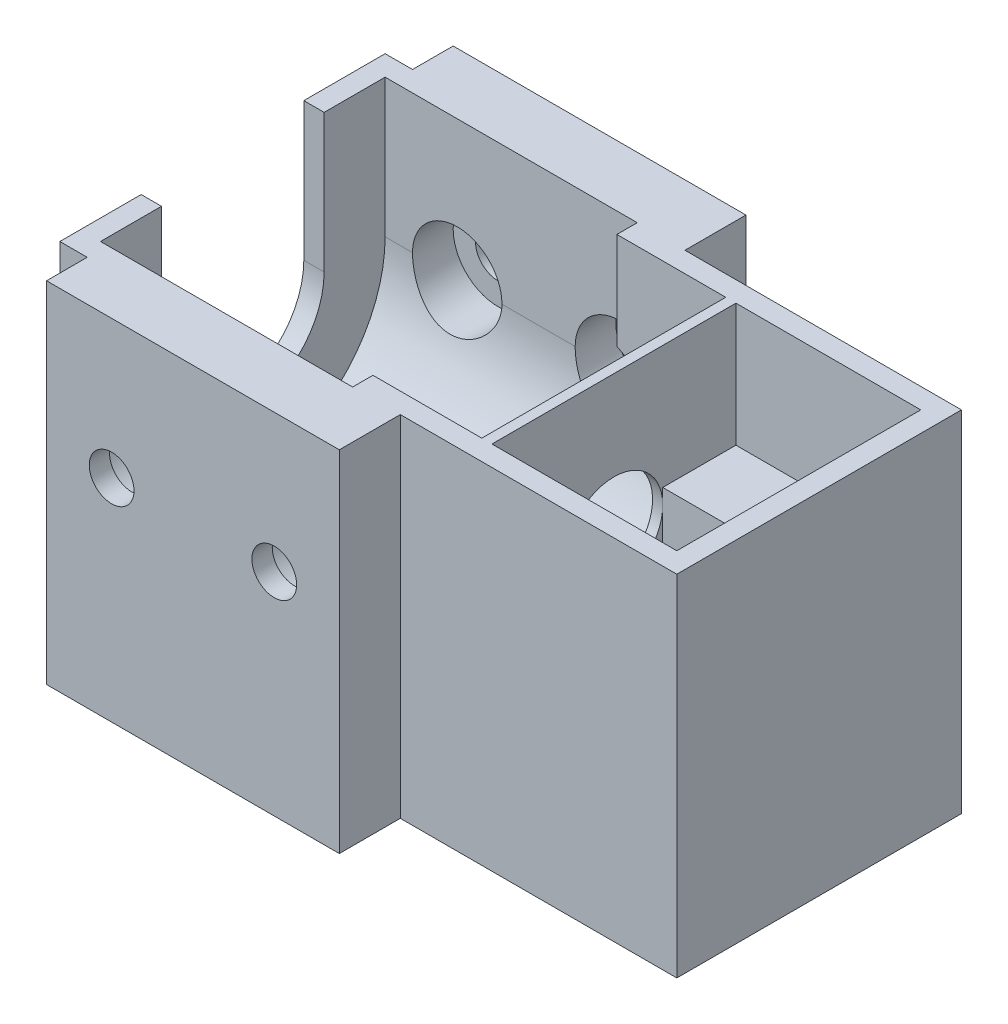
SolidWorks part; units mm, degrees
ref_plane "Front Plane" through (0, 0, 0) normal (0, 0, 1) x (1, 0, 0)
ref_plane "Top Plane" through (0, 0, 0) normal (0, 1, 0) x (1, 0, 0)
ref_plane "Right Plane" through (0, 0, 0) normal (1, 0, 0) x (0, 0, -1)
sketch "Sketch1" plane through (0, 0, 0) normal (0, 0, 1) x (1, 0, 0)
  line L1 (-76.2, -50.8) -> (40.64, -50.8)
  line L2 (-76.2, -50.8) -> (-76.2, 0)
  line L3 (-76.2, 0) -> (40.64, 0)
  line L4 (40.64, -50.8) -> (40.64, 0)
  line L5 (-76.2, -50.8) -> (40.64, 0) construction
  line L6 (-76.2, 0) -> (40.64, -50.8) construction
  point P0 (0, 0)
  dimension "D1" = 116.84
  dimension "D2" = 50.8
  dimension "D3" = 76.2
extrude "Boss-Extrude1" add sketch "Sketch1" along normal mid plane 63.5
sketch "Sketch2" plane through (0, 0, 0) normal (0, 0, 1) x (1, 0, 0)
  line L0 (-152.4829, -25.4) -> (9.3782, -25.4) construction
  line L1 (-49.3609, -3.175) -> (-49.3609, -12.7)
  line L2 (40.64, 0) -> (-76.2, 0) construction
  line L3 (40.64, 0) -> (-76.2, 0) construction
  line L4 (-9.9909, -3.175) -> (-9.9909, -6.35)
  line L5 (-9.9909, -25.4) -> (-9.9909, -3.175) construction
  line L6 (-128.4172, -25.4) -> (-157.8092, -25.4)
  line L7 (9.3782, -25.4) -> (40.64, -25.4)
  line L8 (-607.3619, -25.4) -> (9.3782, -25.4) construction
  line L9 (-49.3609, -3.175) -> (-9.9909, -3.175)
  line L10 (9.3782, -25.4) -> (-128.4172, -25.4)
  line L11 (-9.9909, -6.35) -> (7.0091, -6.35)
  line L12 (7.0091, -6.35) -> (7.0091, -17.78)
  line L13 (7.0091, -17.78) -> (25.0091, -17.78)
  line L14 (-49.3609, -12.7) -> (-220.2024, -12.7)
  line L15 (-220.2024, -12.7) -> (-220.2024, -25.4)
  line L16 (-220.2024, -25.4) -> (-157.8092, -25.4)
  line L17 (25.0091, -17.78) -> (25.0091, -25.4) construction
  line L18 (25.0091, -17.78) -> (40.64, -17.78)
  line L19 (40.64, -50.8) -> (40.64, 0) construction
  line L20 (40.64, -17.78) -> (40.64, -25.4)
  line L21 (-76.2, 0) -> (-76.2, -50.8) construction
  point P23 (-9.9909, -25.4)
  dimension "D1" = 22.225
  dimension "D2" = 39.37
  dimension "D3" = 25.4
  dimension "D4" = 35
  dimension "D5" = 7.62
  dimension "D6" = 3.175
  dimension "D7" = 26.8391
  dimension "D8" = 18
  dimension "D9" = 12.7
revolve "Cut-Revolve1" cut sketch "Sketch2" angle 360 about L0
sketch "Sketch38" plane through (40.64, 0, 0) normal (1, 0, 0) x (0, 0, -1)
  line L1 (-10, -35.4) -> (10, -35.4)
  line L2 (-10, -35.4) -> (-10, -15.4)
  line L3 (-10, -15.4) -> (10, -15.4)
  line L4 (10, -35.4) -> (10, -15.4)
  line L5 (-10, -35.4) -> (10, -15.4) construction
  line L6 (-10, -15.4) -> (10, -35.4) construction
  point P0 (0, -25.4)
  point P1 (0, -25.4)
  dimension "D1" = 20
  dimension "D2" = 20
extrude "Cut-Extrude33" cut sketch "Sketch38" against normal offset from surface (32.0434 mm away) 1.5875 up to face at (7.0091, -44.45, 0)
sketch "Sketch37" plane through (40.64, 0, 0) normal (1, 0, 0) x (0, 0, -1)
  line L0 (31.75, -50.8) -> (31.75, 0) construction
  line L1 (-31.75, 0) -> (31.75, 0)
  line L2 (-31.75, 0) -> (-31.75, -25.4)
  line L3 (-31.75, -25.4) -> (31.75, -25.4)
  line L4 (31.75, 0) -> (31.75, -25.4)
  line L5 (10, -35.4) -> (10, -15.4) construction
  point P7 (0, -25.4)
  point P11 (0, 0)
  point P14 (10, -25.4)
extrude "Cut-Extrude32" cut sketch "Sketch37" against normal through all
sketch "Sketch39" plane through (0, -25.4, 0) normal (0, 1, 0) x (1, 0, 0)
  line L10 (-76.2, 12.7) -> (-49.3609, 12.7)
  line L11 (-49.3609, 12.7) -> (-49.3609, 22.225)
  line L12 (-49.3609, 22.225) -> (-9.9909, 22.225)
  line L13 (-9.9909, 22.225) -> (-9.9909, 19.05)
  line L14 (-9.9909, 19.05) -> (7.0091, 19.05)
  line L15 (7.0091, 19.05) -> (7.0091, 7.62)
  line L16 (7.0091, 19.05) -> (7.0091, 7.62)
  line L17 (40.64, 10) -> (40.64, 31.75)
  line L18 (40.64, 31.75) -> (-76.2, 31.75)
  line L19 (-76.2, 31.75) -> (-76.2, 12.7)
  line L20 (-76.2, 12.7) -> (-49.3609, 12.7)
  line L21 (-49.3609, 12.7) -> (-49.3609, 22.225)
  line L22 (-49.3609, 22.225) -> (-9.9909, 22.225)
  line L23 (-9.9909, 22.225) -> (-9.9909, 19.05)
  line L24 (-9.9909, 19.05) -> (7.0091, 19.05)
  line L25 (8.5966, 10) -> (40.64, 10)
  line L26 (8.5966, 10) -> (40.64, 10)
  line L27 (40.64, 10) -> (40.64, 31.75)
  line L28 (40.64, 31.75) -> (-76.2, 31.75)
  line L29 (-76.2, 31.75) -> (-76.2, 12.7)
  line L30 (-49.3609, -12.7) -> (-76.2, -12.7)
  line L31 (-76.2, -12.7) -> (-76.2, -31.75)
  line L32 (-76.2, -31.75) -> (40.64, -31.75)
  line L33 (40.64, -31.75) -> (40.64, -10)
  line L34 (40.64, -10) -> (8.5966, -10)
  line L35 (40.64, -10) -> (8.5966, -10)
  line L36 (7.0091, -19.05) -> (-9.9909, -19.05)
  line L37 (-9.9909, -19.05) -> (-9.9909, -22.225)
  line L38 (-9.9909, -22.225) -> (-49.3609, -22.225)
  line L39 (-49.3609, -22.225) -> (-49.3609, -12.7)
  line L40 (-49.3609, -12.7) -> (-76.2, -12.7)
  line L41 (-76.2, -12.7) -> (-76.2, -31.75)
  line L42 (-76.2, -31.75) -> (40.64, -31.75)
  line L43 (40.64, -31.75) -> (40.64, -10)
  line L44 (7.0091, -7.62) -> (7.0091, -19.05)
  line L45 (7.0091, -7.62) -> (7.0091, -19.05)
  line L46 (7.0091, -19.05) -> (-9.9909, -19.05)
  line L47 (-9.9909, -19.05) -> (-9.9909, -22.225)
  line L48 (-9.9909, -22.225) -> (-49.3609, -22.225)
  line L49 (-49.3609, -22.225) -> (-49.3609, -12.7)
  line L52 (7.0091, 7.62) -> (8.5966, 7.62)
  line L53 (7.0091, 7.62) -> (8.5966, 7.62)
  line L54 (8.5966, 7.62) -> (8.5966, 10)
  line L55 (8.5966, 7.62) -> (8.5966, 10)
  line L56 (8.5966, -10) -> (8.5966, -7.62)
  line L57 (8.5966, -10) -> (8.5966, -7.62)
  line L58 (8.5966, -7.62) -> (7.0091, -7.62)
  line L59 (8.5966, -7.62) -> (7.0091, -7.62)
  dimension "D1" = 0
  dimension "D2" = 0
extrude "Boss-Extrude5" add sketch "Sketch39" along normal blind 25.4
sketch "Sketch40" plane through (0, 0, 0) normal (0, 1, 0) x (1, 0, 0)
  line L0 (8.5966, 10) -> (40.64, 10) construction
  line L1 (25.0091, 10) -> (40.64, 10)
  line L2 (25.0091, 10) -> (25.0091, -10)
  line L3 (25.0091, -10) -> (40.64, -10)
  line L4 (40.64, 10) -> (40.64, -10)
  line L6 (-9.9909, 22.225) -> (-9.9909, 19.05) construction
  dimension "D1" = 35
extrude "Boss-Extrude6" add sketch "Sketch40" against normal up to next
sketch "Sketch41" plane through (0, 0, 0) normal (0, 1, 0) x (1, 0, 0)
  line L2 (-76.2, 12.7) -> (-76.2, -12.7) construction
  circle A0 centre (-57.15, 0) radius 3.1134
  circle A1 centre (-31.75, 0) radius 3.1134
  circle A2 centre (-6.35, 0) radius 3.1134
  dimension "D1" = 19.05
extrude "Cut-Extrude34" cut sketch "Sketch41" against normal through all
ref_plane "Plane_Mid" through (0, -25.4, 0) normal (0, 1, 0) x (1, 0, 0)
ref_axis "Axis1" through (8.5966, -25.4, 0) along (-1, 0, 0)
sketch "Sketch42" plane through (0, 0, 0) normal (0, 0, 1) x (1, 0, 0)
  line L0 (1.7462, -25.4) -> (-1.7462, -25.4) construction
  line L1 (-76.2, 0) -> (-76.2, -25.4) construction
  circle A0 centre (-38.1, -25.4) radius 3.4925
  circle A1 centre (-12.7, -25.4) radius 3.4925
  dimension "D1" = 6.985
  dimension "D2" = 38.1
extrude "Cut-Extrude35" cut sketch "Sketch42" against normal through all both and the other way through all
sketch "Sketch43" plane through (0, 0, 0) normal (0, 0, 1) x (1, 0, 0)
  circle A0 centre (-38.1, -25.4) radius 6.985
  circle A1 centre (-12.7, -25.4) radius 6.985
  dimension "D1" = 13.97
extrude "Cut-Extrude36" cut sketch "Sketch43" against normal offset from surface (28.575 mm away) 3.175 up to face at (-9.2075, -25.4, -31.75)
extrude "Cut-Extrude37" cut sketch "Sketch43<2>" along normal offset from surface (28.575 mm away) 3.175 up to face at (-9.2075, -25.4, 31.75)
sketch "Sketch43<2>" plane through (0, 0, 0) normal (0, 0, 1) x (1, 0, 0) same geometry as "Sketch43"
sketch "Sketch44" plane through (0, 0, 0) normal (0, 1, 0) x (1, 0, 0)
  line L0 (7.0091, -19.05) -> (-9.9909, -19.05) construction
  line L1 (8.5966, 19.05) -> (24.5091, 19.05)
  line L2 (8.5966, 19.05) -> (8.5966, -19.05)
  line L3 (8.5966, -19.05) -> (24.5091, -19.05)
  line L4 (24.5091, 19.05) -> (24.5091, -19.05)
  line L5 (-9.9909, 19.05) -> (7.0091, 19.05) construction
  line L6 (8.5966, 7.62) -> (8.5966, 10) construction
  line L7 (25.0091, 10) -> (25.0091, -10) construction
  dimension "D1" = 0.5
extrude "Cut-Extrude38" cut sketch "Sketch44" against normal up to surface (35.4 mm away) up to face at (16.8028, -35.4, 0)
sketch "Sketch45" plane through (0, 0, 0) normal (0, 0, 1) x (1, 0, 0)
  line L0 (40.64, 0) -> (-76.2, 0) construction
  line L2 (37.465, 0) -> (24.5091, 0)
  line L4 (37.465, 0) -> (37.465, -15.4)
  line L5 (37.465, -15.4) -> (24.5091, -15.4)
  line L8 (24.5091, 0) -> (24.5091, -15.4)
  line L9 (40.64, -50.8) -> (40.64, 0) construction
  line L10 (24.5091, -35.4) -> (24.5091, 0) construction
  line L11 (-5.715, -25.4) -> (7.0091, -25.4) construction
  dimension "D1" = 3.175
  dimension "D2" = 10
extrude "Cut-Extrude39" cut sketch "Sketch45" against normal up to surface and the other way up to surface up to face at (16.5528, -17.7, -19.05) other way up to face at (16.5529, -17.7, 19.05)
sketch "Sketch46" plane through (0, 0, 0) normal (0, 1, 0) x (1, 0, 0)
  line L0 (-9.9909, 19.05) -> (7.0091, 19.05) construction
  line L1 (40.64, 31.75) -> (-2.54, 31.75)
  line L2 (40.64, 31.75) -> (40.64, 22.225)
  line L3 (40.64, 22.225) -> (-2.54, 22.225)
  line L4 (-2.54, 31.75) -> (-2.54, 22.225)
  line L5 (-76.2, 0) -> (40.64, 0) construction
  line L6 (-76.2, 12.7) -> (-76.2, -12.7) construction
  line L7 (40.64, -31.75) -> (40.64, 31.75) construction
  line L8 (40.64, -31.75) -> (40.64, -22.225)
  line L9 (40.64, -22.225) -> (-2.54, -22.225)
  line L10 (40.64, -31.75) -> (-2.54, -31.75)
  line L11 (-2.54, -31.75) -> (-2.54, -22.225)
  line L12 (-49.3609, 22.225) -> (-9.9909, 22.225) construction
  line L13 (-76.2, 31.75) -> (-48.26, 31.75)
  line L14 (-76.2, 31.75) -> (-76.2, 25.4)
  line L15 (-76.2, 25.4) -> (-48.26, 25.4)
  line L16 (-48.26, 31.75) -> (-48.26, 25.4)
  line L17 (-48.26, -31.75) -> (-48.26, -25.4)
  line L18 (-76.2, -25.4) -> (-48.26, -25.4)
  line L19 (-76.2, -31.75) -> (-76.2, -25.4)
  line L20 (-76.2, -31.75) -> (-48.26, -31.75)
  dimension "D1" = 3.175
  dimension "D2" = 3.175
  dimension "D3" = 3.175
  dimension "D4" = 3.175
extrude "Cut-Extrude40" cut sketch "Sketch46" against normal through all
sketch "Sketch49" plane through (0, 0, 0) normal (0, 1, 0) x (1, 0, 0)
  line L0 (-48.26, -25.4) -> (-76.2, -25.4) construction
  line L1 (-76.2, 25.4) -> (-52.5359, 25.4)
  line L2 (-76.2, 25.4) -> (-76.2, -25.4)
  line L3 (-76.2, -25.4) -> (-52.5359, -25.4)
  line L4 (-52.5359, 25.4) -> (-52.5359, -25.4)
  line L5 (-49.3609, -22.225) -> (-49.3609, 22.225) construction
  dimension "D1" = 3.175
extrude "Cut-Extrude42" cut sketch "Sketch49" against normal through all
sketch "Sketch50" plane through (0, 0, 0) normal (0, 1, 0) x (1, 0, 0)
  line L0 (-2.54, 22.225) -> (40.64, 22.225) construction
  line L1 (24.2551, 20.701) -> (24.5091, 20.701)
  line L2 (24.2551, 20.701) -> (24.2551, 22.225)
  line L3 (24.2551, 22.225) -> (24.5091, 22.225)
  line L4 (24.5091, 20.701) -> (24.5091, 22.225)
  line L5 (24.3821, 22.225) -> (24.3821, 20.701) construction
  line L6 (24.2551, 21.463) -> (24.5091, 21.463) construction
  line L8 (24.5091, 10) -> (24.5091, 19.05) construction
  line L9 (22.7311, 20.701) -> (22.9851, 20.701)
  line L10 (22.9851, 20.701) -> (22.9851, 22.225)
  line L11 (22.7311, 22.225) -> (22.9851, 22.225)
  line L12 (22.7311, 20.701) -> (22.7311, 22.225)
  line L13 (21.2071, 20.701) -> (21.4611, 20.701)
  line L14 (21.4611, 20.701) -> (21.4611, 22.225)
  line L15 (21.2071, 22.225) -> (21.4611, 22.225)
  line L16 (21.2071, 20.701) -> (21.2071, 22.225)
  line L17 (19.6831, 20.701) -> (19.9371, 20.701)
  line L18 (19.9371, 20.701) -> (19.9371, 22.225)
  line L19 (19.6831, 22.225) -> (19.9371, 22.225)
  line L20 (19.6831, 20.701) -> (19.6831, 22.225)
  line L21 (18.1591, 20.701) -> (18.4131, 20.701)
  line L22 (18.4131, 20.701) -> (18.4131, 22.225)
  line L23 (18.1591, 22.225) -> (18.4131, 22.225)
  line L24 (18.1591, 20.701) -> (18.1591, 22.225)
  line L25 (16.6351, 20.701) -> (16.8891, 20.701)
  line L26 (16.8891, 20.701) -> (16.8891, 22.225)
  line L27 (16.6351, 22.225) -> (16.8891, 22.225)
  line L28 (16.6351, 20.701) -> (16.6351, 22.225)
  line L29 (15.1111, 20.701) -> (15.3651, 20.701)
  line L30 (15.3651, 20.701) -> (15.3651, 22.225)
  line L31 (15.1111, 22.225) -> (15.3651, 22.225)
  line L32 (15.1111, 20.701) -> (15.1111, 22.225)
  line L33 (13.5871, 20.701) -> (13.8411, 20.701)
  line L34 (13.8411, 20.701) -> (13.8411, 22.225)
  line L35 (13.5871, 22.225) -> (13.8411, 22.225)
  line L36 (13.5871, 20.701) -> (13.5871, 22.225)
  line L37 (12.0631, 20.701) -> (12.3171, 20.701)
  line L38 (12.3171, 20.701) -> (12.3171, 22.225)
  line L39 (12.0631, 22.225) -> (12.3171, 22.225)
  line L40 (12.0631, 20.701) -> (12.0631, 22.225)
  line L41 (10.5391, 20.701) -> (10.7931, 20.701)
  line L42 (10.7931, 20.701) -> (10.7931, 22.225)
  line L43 (10.5391, 22.225) -> (10.7931, 22.225)
  line L44 (10.5391, 20.701) -> (10.5391, 22.225)
  point P0 (24.3821, 21.463)
  dimension "D1" = 0.254
  dimension "D2" = 1.524
  dimension "D3" = 10
extrude "Cut-Extrude43" cut sketch "Sketch50" against normal blind 2.54
sketch "Sketch52" plane through (25.0091, 0, 0) normal (-1, 0, 0) x (0, 0, 1)
  circle A0 centre (0, -25.4) radius 0.3175
  dimension "D1" = 0.635
extrude "Cut-Extrude45" cut sketch "Sketch52" against normal blind 0.0508
sketch "Sketch53" plane through (25.0091, 0, 0) normal (-1, 0, 0) x (0, 0, 1)
  circle A0 centre (0, -25.4) radius 2
  dimension "D1" = 4
extrude "Cut-Extrude46" cut sketch "Sketch53" against normal blind 0.0254
sketch "Sketch54" plane through (0, -35.4, 0) normal (0, 1, 0) x (1, 0, 0)
  line L0 (24.5091, 10) -> (24.5091, -10)
  line L8 (25.0091, 10) -> (24.5091, 10)
  line L9 (24.5091, 10) -> (24.5091, 19.05)
  line L10 (24.5091, 19.05) -> (8.5966, 19.05)
  line L11 (8.5966, 19.05) -> (8.5966, -19.05)
  line L12 (8.5966, -19.05) -> (24.5091, -19.05)
  line L13 (24.5091, -19.05) -> (24.5091, -10)
  line L14 (24.5091, -10) -> (25.0091, -10)
  line L15 (25.0091, -10) -> (25.0091, 10)
  line L17 (24.5091, 10) -> (24.5091, 19.05)
  line L18 (24.5091, 19.05) -> (8.5966, 19.05)
  line L19 (8.5966, 19.05) -> (8.5966, -19.05)
  line L20 (8.5966, -19.05) -> (24.5091, -19.05)
  line L21 (24.5091, -19.05) -> (24.5091, -10)
  dimension "D1" = 0
extrude "Boss-Extrude7" add sketch "Sketch54" along normal blind 2.54
sketch "Sketch55" plane through (0, -32.86, 0) normal (0, 1, 0) x (1, 0, 0)
  line L0 (24.5091, -19.05) -> (24.5091, -10) construction
  line L1 (24.5091, 10) -> (8.5966, 10)
  line L2 (24.5091, 10) -> (24.5091, 19.05)
  line L3 (24.5091, 19.05) -> (8.5966, 19.05)
  line L4 (8.5966, 10) -> (8.5966, 19.05)
  line L5 (24.5091, 10) -> (8.5966, 19.05) construction
  line L6 (24.5091, 19.05) -> (8.5966, 10) construction
  line L7 (8.5966, -19.05) -> (24.5091, -19.05)
  line L8 (8.5966, -19.05) -> (8.5966, -10)
  line L9 (8.5966, -10) -> (24.5091, -10)
  line L10 (24.5091, -19.05) -> (24.5091, -10)
  line L11 (8.5966, -19.05) -> (24.5091, -10) construction
  line L12 (8.5966, -10) -> (24.5091, -19.05) construction
  point P4 (16.5528, 14.525)
  point P11 (16.5528, -14.525)
extrude "Boss-Extrude8" add sketch "Sketch55" along normal up to surface (17.46 mm away) up to face at (27.8731, -15.4, 0)
sketch "Sketch56" plane through (0, 0, 0) normal (0, 0, 1) x (1, 0, 0)
  line L0 (18.1591, -27.4) -> (18.1591, -32.86) construction
  line L1 (25.0345, -27.4) -> (18.1591, -27.4) construction
  line L2 (25.0345, -23.4) -> (25.0345, -27.4) construction
  line L3 (8.5966, -25.4) -> (7.0091, -25.4) construction
  line L4 (8.5966, -32.86) -> (8.5966, -25.4) construction
  line L5 (13.3779, -30.13) -> (8.5966, -30.13) construction
  line L6 (13.3779, -30.13) -> (18.1591, -30.13) construction
  line L7 (18.1591, -27.4) -> (24.5091, -27.4)
  line L8 (24.5091, -27.4) -> (24.5091, -32.86)
  line L9 (8.5966, -32.86) -> (24.5091, -32.86)
  spline S0 degree 3 poles (8.5966, -32.86) (9.5288, -32.86) (16.4945, -27.986) (16.8413, -27.4) (18.1591, -27.4) knots 0 0 0 0 0.327131 1 1 1 1
  point P6 (18.1591, -30.13)
  dimension "D1" = 2
  dimension "D2" = 6.35
extrude "Boss-Extrude9" add sketch "Sketch56" along normal up to next and the other way up to next
sketch "Sketch57" plane through (0, -15.4, 0) normal (0, 1, 0) x (1, 0, 0)
  line L8 (25.0091, -10) -> (8.5966, -10)
  line L9 (8.5966, -10) -> (8.5966, -19.05)
  line L10 (8.5966, -19.05) -> (37.465, -19.05)
  line L11 (37.465, -19.05) -> (37.465, 19.05)
  line L12 (37.465, 19.05) -> (8.5966, 19.05)
  line L13 (25.0091, -10) -> (8.5966, -10)
  line L14 (8.5966, 19.05) -> (8.5966, 10)
  line L15 (25.0091, 10) -> (25.0091, -10)
  line L16 (8.5966, 19.05) -> (8.5966, 10)
  line L17 (8.5966, -10) -> (8.5966, -19.05)
  line L18 (8.5966, -19.05) -> (37.465, -19.05)
  line L19 (37.465, -19.05) -> (37.465, 19.05)
  line L20 (37.465, 19.05) -> (8.5966, 19.05)
  line L21 (8.5966, 10) -> (25.0091, 10)
  line L22 (8.5966, 10) -> (25.0091, 10)
  line L23 (25.0091, 10) -> (25.0091, -10)
  dimension "D1" = 0
extrude "Cut-Extrude47" cut sketch "Sketch57" against normal blind 7.62
sketch "Sketch58" plane through (0, -50.8, 0) normal (0, -1, 0) x (1, 0, 0)
  line L12 (-48.26, 25.4) -> (-52.5359, 25.4)
  line L13 (-52.5359, 25.4) -> (-52.5359, -25.4)
  line L14 (-52.5359, -25.4) -> (-48.26, -25.4)
  line L15 (-48.26, -25.4) -> (-48.26, -31.75)
  line L16 (-48.26, -31.75) -> (-2.54, -31.75)
  line L17 (-2.54, -31.75) -> (-2.54, -22.225)
  line L18 (-2.54, -22.225) -> (40.64, -22.225)
  line L19 (40.64, -22.225) -> (40.64, 22.225)
  line L20 (40.64, 22.225) -> (-2.54, 22.225)
  line L21 (-2.54, 22.225) -> (-2.54, 31.75)
  line L22 (-2.54, 31.75) -> (-48.26, 31.75)
  line L23 (-48.26, 31.75) -> (-48.26, 25.4)
  line L24 (-48.26, 25.4) -> (-52.5359, 25.4)
  line L25 (-52.5359, 25.4) -> (-52.5359, -25.4)
  line L26 (-52.5359, -25.4) -> (-48.26, -25.4)
  line L27 (-48.26, -25.4) -> (-48.26, -31.75)
  line L28 (-48.26, -31.75) -> (-2.54, -31.75)
  line L29 (-2.54, -31.75) -> (-2.54, -22.225)
  line L30 (-2.54, -22.225) -> (40.64, -22.225)
  line L31 (40.64, -22.225) -> (40.64, 22.225)
  line L32 (40.64, 22.225) -> (-2.54, 22.225)
  line L33 (-2.54, 22.225) -> (-2.54, 31.75)
  line L34 (-2.54, 31.75) -> (-48.26, 31.75)
  line L35 (-48.26, 31.75) -> (-48.26, 25.4)
  circle A0 centre (-31.75, 0) radius 3.1134
  circle A1 centre (-6.35, 0) radius 3.1134
  circle A2 centre (-6.35, 0) radius 3.1134 construction
  circle A3 centre (-31.75, 0) radius 3.1134 construction
  dimension "D1" = 0
extrude "Boss-Extrude10" add sketch "Sketch58" along normal blind 7.62
sketch "Sketch59" plane through (0, -35.4, 0) normal (0, 1, 0) x (1, 0, 0)
  line L4 (24.5091, 10) -> (24.5091, -10)
  line L5 (24.5091, -10) -> (25.0091, -10)
  line L6 (25.0091, -10) -> (25.0091, 10)
  line L7 (25.0091, 10) -> (24.5091, 10)
  line L8 (24.5091, 10) -> (24.5091, -10)
  line L9 (24.5091, -10) -> (25.0091, -10)
  line L10 (25.0091, -10) -> (25.0091, 10)
  line L11 (25.0091, 10) -> (24.5091, 10)
  dimension "D1" = 0
extrude "Cut-Extrude48" cut sketch "Sketch59" against normal blind 7.62
sketch "Sketch51" plane through (0, -23.02, 0) normal (0, 1, 0) x (1, 0, 0)
  line L0 (26.2025, 0.254) -> (27.2127, 0.254)
  line L1 (25.6945, 2.54) -> (26.2025, 2.54)
  line L2 (25.6945, 2.54) -> (25.6945, 0.254)
  line L3 (25.6945, -2.54) -> (26.2025, -2.54)
  line L4 (26.2025, 2.54) -> (26.2025, 0.254)
  line L5 (30.7571, -0.254) -> (31.7673, -0.254)
  line L6 (26.2025, -0.254) -> (26.2025, -2.54)
  line L7 (27.7207, 2.54) -> (27.7207, 0.254)
  line L8 (27.2127, 2.54) -> (27.7207, 2.54)
  line L9 (27.2127, 2.54) -> (27.2127, 0.254)
  line L10 (27.2127, -2.54) -> (27.7207, -2.54)
  line L11 (29.2389, 2.54) -> (29.2389, 0.254)
  line L12 (28.7309, 2.54) -> (29.2389, 2.54)
  line L13 (28.7309, 2.54) -> (28.7309, 0.254)
  line L14 (28.7309, -2.54) -> (29.2389, -2.54)
  line L15 (30.7571, 2.54) -> (30.7571, 0.254)
  line L16 (30.2491, 2.54) -> (30.7571, 2.54)
  line L17 (30.2491, 2.54) -> (30.2491, 0.254)
  line L18 (30.2491, -2.54) -> (30.7571, -2.54)
  line L19 (32.2753, 2.54) -> (32.2753, 0.254)
  line L20 (31.7673, 2.54) -> (32.2753, 2.54)
  line L21 (31.7673, 2.54) -> (31.7673, 0.254)
  line L22 (31.7673, -2.54) -> (32.2753, -2.54)
  line L23 (33.7936, 2.54) -> (33.7936, 0.254)
  line L24 (33.2856, 2.54) -> (33.7936, 2.54)
  line L25 (33.2856, 2.54) -> (33.2856, 0.254)
  line L26 (33.2856, -2.54) -> (33.7936, -2.54)
  line L27 (35.3118, 2.54) -> (35.3118, 0.254)
  line L28 (34.8038, 2.54) -> (35.3118, 2.54)
  line L29 (34.8038, 2.54) -> (34.8038, 0.254)
  line L30 (34.8038, -2.54) -> (35.3118, -2.54)
  line L31 (36.83, 2.54) -> (36.83, 0.254)
  line L32 (36.322, 2.54) -> (36.83, 2.54)
  line L33 (36.322, 2.54) -> (36.322, 0.254)
  line L34 (36.322, -2.54) -> (36.83, -2.54)
  line L35 (35.258, 2.5876) -> (25.851, 2.5876) construction
  line L36 (23.32, 11.7754) -> (37.465, 11.7754) construction
  line L37 (26.2025, -0.254) -> (27.2127, -0.254)
  line L38 (25.0091, 10) -> (25.0091, -10) construction
  line L39 (37.465, -19.05) -> (37.465, 19.05) construction
  line L40 (25.0091, 0.254) -> (25.6945, 0.254)
  line L41 (25.0091, 0.254) -> (25.0091, -0.254)
  line L42 (25.0091, -0.254) -> (25.6945, -0.254)
  line L43 (37.465, 0.254) -> (37.465, -0.254)
  line L44 (32.2753, 0.254) -> (33.2856, 0.254)
  line L46 (25.6945, -0.254) -> (25.6945, -2.54)
  line L47 (27.2127, -0.254) -> (27.2127, -2.54)
  line L48 (27.7207, 0.254) -> (28.7309, 0.254)
  line L49 (27.7207, -0.254) -> (27.7207, -2.54)
  line L51 (27.7207, -0.254) -> (28.7309, -0.254)
  line L52 (28.7309, -0.254) -> (28.7309, -2.54)
  line L53 (29.2389, 0.254) -> (30.2491, 0.254)
  line L54 (29.2389, -0.254) -> (30.2491, -0.254)
  line L55 (29.2389, -0.254) -> (29.2389, -2.54)
  line L56 (30.2491, -0.254) -> (30.2491, -2.54)
  line L57 (30.7571, 0.254) -> (31.7673, 0.254)
  line L58 (32.2753, -0.254) -> (33.2856, -0.254)
  line L61 (30.7571, -0.254) -> (30.7571, -2.54)
  line L62 (31.7673, -0.254) -> (31.7673, -2.54)
  line L63 (32.2753, -0.254) -> (32.2753, -2.54)
  line L64 (33.2856, -0.254) -> (33.2856, -2.54)
  line L65 (33.7936, 0.254) -> (34.8038, 0.254)
  line L66 (33.7936, -0.254) -> (34.8038, -0.254)
  line L67 (33.7936, -0.254) -> (33.7936, -2.54)
  line L68 (34.8038, -0.254) -> (34.8038, -2.54)
  line L69 (35.3118, 0.254) -> (36.322, 0.254)
  line L70 (35.3118, -0.254) -> (36.322, -0.254)
  line L71 (35.3118, -0.254) -> (35.3118, -2.54)
  line L72 (36.322, -0.254) -> (36.322, -2.54)
  line L73 (36.83, -0.254) -> (36.83, -2.54)
  line L74 (36.83, 0.254) -> (37.465, 0.254)
  line L75 (36.83, -0.254) -> (37.465, -0.254)
  text T1 "<b>v8</b>"
  point P0 (24.717, 0)
  point P51 (30.3925, 0)
  point P52 (25.0091, 0)
  dimension "D1" = 0.508
  dimension "D2" = 5.08
  dimension "D3" = 1.5182
  dimension "D5" = 0.8419
  dimension "D6" = 0.508
  dimension "D7" = 0.635
  dimension "D4" = 8
extrude "Cut-Label" cut sketch "Sketch51" against normal blind 0.635
sketch "Sketch60" plane through (0, 0, 0) normal (0, 1, 0) x (1, 0, 0)
  line L1 (-60.6783, -40.5295) -> (60.6783, -40.5295)
  line L2 (-60.6783, -40.5295) -> (-60.6783, 40.5295)
  line L3 (-60.6783, 40.5295) -> (60.6783, 40.5295)
  line L4 (60.6783, -40.5295) -> (60.6783, 40.5295)
  line L5 (0, 40.5295) -> (0, -40.5295) construction
  line L6 (-60.6783, 0) -> (60.6783, 0) construction
  point P0 (0, 0)
extrude "Cut-Extrude49" cut sketch "Sketch60" against normal blind 10.16
ref_plane "Plane_Bottom" through (0, -47.625, 0) normal (0, 1, 0) x (1, 0, 0)
ref_plane "Plane_Top" through (0, -3.81, 0) normal (0, 1, 0) x (1, 0, 0)
sketch "Sketch61" plane through (7.0091, 0, 0) normal (-1, 0, 0) x (0, 0, 1)
  circle A0 centre (0, -25.4) radius 7.62
  circle A1 centre (0, -25.4) radius 8.9762
extrude "Boss-Extrude11" add sketch "Sketch61" against normal up to surface (1.5875 mm away) up to face at (8.5966, -21.9643, -11.7357)
sketch "Sketch62" plane through (0, -10.16, 0) normal (0, 1, 0) x (1, 0, 0)
  line L1 (8.5966, 7.62) -> (7.0091, 7.62)
  line L2 (8.5966, 7.62) -> (8.5966, -7.62)
  line L3 (8.5966, -7.62) -> (7.0091, -7.62)
  line L4 (7.0091, 7.62) -> (7.0091, -7.62)
  line L5 (8.5966, 7.62) -> (7.0091, -7.62) construction
  line L6 (8.5966, -7.62) -> (7.0091, 7.62) construction
  point P4 (7.8028, 0)
extrude "Boss-Extrude12" add sketch "Sketch62" against normal up to next
sketch "Sketch64" plane through (0, -10.16, 0) normal (0, 1, 0) x (1, 0, 0)
  line L25 (37.465, 19.05) -> (8.5966, 19.05)
  line L26 (37.465, 19.05) -> (37.465, -19.05)
  line L27 (37.465, -19.05) -> (8.5966, -19.05)
  line L28 (8.5966, 19.05) -> (8.5966, -19.05)
  line L29 (37.465, 19.05) -> (8.5966, -19.05) construction
  line L30 (37.465, -19.05) -> (8.5966, 19.05) construction
  line L48 (-9.9909, 19.05) -> (7.0091, 19.05)
  line L49 (7.0091, 19.05) -> (7.0091, -19.05)
  line L50 (7.0091, -19.05) -> (-9.9909, -19.05)
  line L51 (-9.9909, -19.05) -> (-9.9909, -22.225)
  line L52 (-9.9909, -22.225) -> (-49.3609, -22.225)
  line L53 (-49.3609, -22.225) -> (-49.3609, -12.7)
  line L54 (-49.3609, -12.7) -> (-52.5359, -12.7)
  line L55 (-52.5359, -12.7) -> (-52.5359, -25.4)
  line L56 (-52.5359, -25.4) -> (-48.26, -25.4)
  line L57 (-48.26, -25.4) -> (-48.26, -31.75)
  line L58 (-48.26, -31.75) -> (-2.54, -31.75)
  line L59 (-2.54, -31.75) -> (-2.54, -22.225)
  line L60 (-2.54, -22.225) -> (40.64, -22.225)
  line L61 (40.64, -22.225) -> (40.64, 22.225)
  line L62 (40.64, 22.225) -> (-2.54, 22.225)
  line L63 (-2.54, 22.225) -> (-2.54, 31.75)
  line L64 (-2.54, 31.75) -> (-48.26, 31.75)
  line L65 (-48.26, 31.75) -> (-48.26, 25.4)
  line L66 (-48.26, 25.4) -> (-52.5359, 25.4)
  line L67 (-52.5359, 25.4) -> (-52.5359, 12.7)
  line L68 (-52.5359, 12.7) -> (-49.3609, 12.7)
  line L69 (-49.3609, 12.7) -> (-49.3609, 22.225)
  line L70 (-49.3609, 22.225) -> (-9.9909, 22.225)
  line L71 (-9.9909, 22.225) -> (-9.9909, 19.05)
  line L72 (-9.9909, 19.05) -> (7.0091, 19.05)
  line L73 (7.0091, 19.05) -> (7.0091, -19.05)
  line L74 (7.0091, -19.05) -> (-9.9909, -19.05)
  line L75 (-9.9909, -19.05) -> (-9.9909, -22.225)
  line L76 (-9.9909, -22.225) -> (-49.3609, -22.225)
  line L77 (-49.3609, -22.225) -> (-49.3609, -12.7)
  line L78 (-49.3609, -12.7) -> (-52.5359, -12.7)
  line L79 (-52.5359, -12.7) -> (-52.5359, -25.4)
  line L80 (-52.5359, -25.4) -> (-48.26, -25.4)
  line L81 (-48.26, -25.4) -> (-48.26, -31.75)
  line L82 (-48.26, -31.75) -> (-2.54, -31.75)
  line L83 (-2.54, -31.75) -> (-2.54, -22.225)
  line L84 (-2.54, -22.225) -> (40.64, -22.225)
  line L85 (40.64, -22.225) -> (40.64, 22.225)
  line L86 (40.64, 22.225) -> (-2.54, 22.225)
  line L87 (-2.54, 22.225) -> (-2.54, 31.75)
  line L88 (-2.54, 31.75) -> (-48.26, 31.75)
  line L89 (-48.26, 31.75) -> (-48.26, 25.4)
  line L90 (-48.26, 25.4) -> (-52.5359, 25.4)
  line L91 (-52.5359, 25.4) -> (-52.5359, 12.7)
  line L92 (-52.5359, 12.7) -> (-49.3609, 12.7)
  line L93 (-49.3609, 12.7) -> (-49.3609, 22.225)
  line L94 (-49.3609, 22.225) -> (-9.9909, 22.225)
  line L95 (-9.9909, 22.225) -> (-9.9909, 19.05)
  point P28 (23.0308, 0)
  dimension "D1" = 0
extrude "Boss-Extrude14" add sketch "Sketch64" along normal up to surface (6.35 mm away) up to plane "Plane_Top"
sketch "Sketch65" plane through (8.5966, 0, 0) normal (1, 0, 0) x (0, 0, -1)
  line L0 (-10, -23.02) -> (-7.62, -23.02)
  line L1 (10, -23.02) -> (7.62, -23.02)
  line L2 (-7.62, -32.86) -> (-7.62, -23.02)
  line L3 (7.62, -32.86) -> (7.62, -23.02)
  line L6 (-10, -23.02) -> (-10, -32.86)
  line L7 (-10, -32.86) -> (-7.62, -32.86)
  line L8 (7.62, -32.86) -> (10, -32.86)
  line L28 (10, -32.86) -> (10, -23.02)
  point P12 (8.81, -23.02)
extrude "Boss-Extrude16" add sketch "Sketch65" along normal up to next
sketch "Sketch66" plane through (0, -23.02, 0) normal (0, 1, 0) x (1, 0, 0)
  line L0 (25.0091, 7.62) -> (25.0091, 0.254) construction
  line L1 (24.5091, 10) -> (25.0091, 10)
  line L2 (24.5091, 10) -> (24.5091, -10)
  line L3 (24.5091, -10) -> (25.0091, -10)
  line L4 (25.0091, 10) -> (25.0091, -10)
  line L5 (24.5091, 10) -> (25.0091, -10) construction
  line L6 (24.5091, -10) -> (25.0091, 10) construction
  line L8 (24.5091, 7.62) -> (24.5091, -7.62) construction
  line L9 (8.5966, 0) -> (7.0091, 0) construction
  point P4 (24.7591, 0)
  dimension "D1" = 20
extrude "Cut-Extrude50" cut sketch "Sketch66" against normal up to surface (20 mm away) up to face at (24.7591, -43.02, 0)
